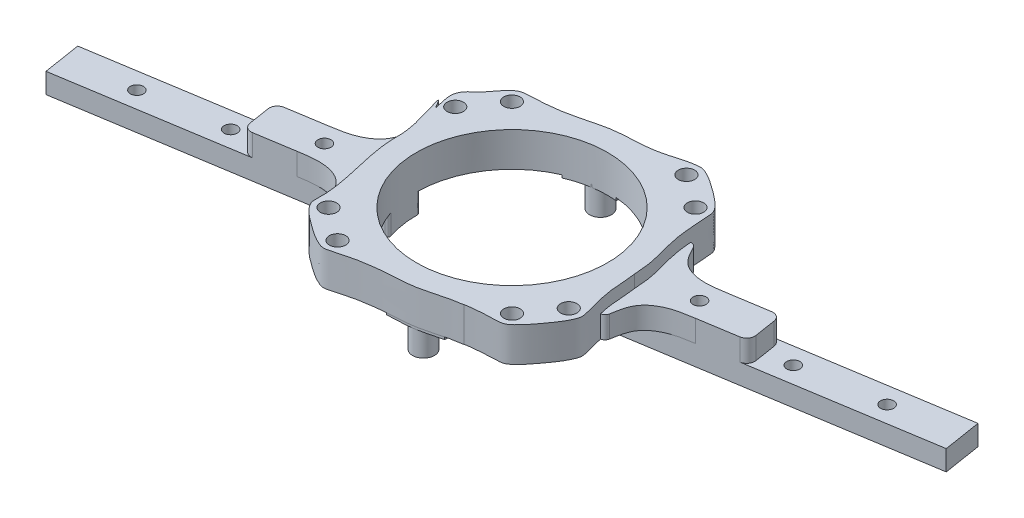
SolidWorks part; units mm, degrees
ref_plane "前视基准面" through (0, 0, 0) normal (0, 0, 1) x (1, 0, 0)
ref_plane "上视基准面" through (0, 0, 0) normal (0, 1, 0) x (1, 0, 0)
ref_plane "右视基准面" through (0, 0, 0) normal (1, 0, 0) x (0, 0, -1)
sketch "草图1" plane through (0, 0, 0) normal (0, 1, 0) x (1, 0, 0)
  circle A0 centre (0, 0) radius 17.5
  circle A1 centre (0, 0) radius 18.901
  dimension "D1" = 35
extrude "凸台-拉伸1" add sketch "草图1" along normal blind 2
sketch "草图2" plane through (0, 0, 0) normal (0, -1, 0) x (1, 0, 0)
  circle A0 centre (-10.7739, 21.1656) radius 1.5
  circle A1 centre (16.8004, 16.7872) radius 1.5
  circle A2 centre (21.1656, 10.7739) radius 1.5
  circle A3 centre (16.7872, -16.8004) radius 1.5
  circle A4 centre (10.7739, -21.1656) radius 1.5
  circle A5 centre (-16.8004, -16.7872) radius 1.5
  circle A6 centre (-21.1656, -10.7739) radius 1.5
  circle A7 centre (-16.7872, 16.8004) radius 1.5
  circle A28 centre (0, 0) radius 17.5
  spline S3 degree 3 poles (11.007, 19.7796) (11.3114, 19.6784) (14.2307, 19.3249) (16.1426, 19.3879) (17.8124, 19.1708) (19.4344, 17.903) (21.2548, 15.4236) (23.0457, 12.9332) (23.7495, 10.9887) (23.274, 8.5261) (21.9734, 4.7628) (22.0269, 1.1873) (21.7447, -0.683) knots 0 0 0 0 0.101498 0.202996 0.236379 0.269761 0.41266 0.555558 0.58894 0.622323 0.811161 1 1 1 1
  spline S4 degree 3 poles (21.7447, -0.683) (21.6101, -1.5752) (21.6055, -3.3542) (20.6884, -6.8809) (19.4904, -11.3054) (19.4855, -15.3122) (19.178, -17.8032) (17.9056, -19.4334) (15.4365, -21.2528) (12.9718, -22.9922) (11.1783, -23.6905) (8.6855, -23.5473) (4.924, -21.9674) (0.2192, -21.8124) (-3.3386, -21.5662) (-6.4463, -20.811) (-9.0785, -20.0903) (-12.7412, -19.4848) (-15.1253, -19.3752) (-17.5836, -19.2474) (-19.4002, -18.127) (-20.9244, -15.1209) (-24.3676, -13.3124) (-22.2966, -7.7817) (-24.7387, -12.2711) (-21.435, -3.3276) (-22.0126, 0.3206) (-20.5515, 8.1406) (-19.1109, 13.0019) (-19.2816, 16.8284) knots 0 0 0 0 0.02817 0.053916 0.112305 0.168269 0.178162 0.188055 0.230405 0.272754 0.280796 0.288838 0.34856 0.404524 0.432694 0.45844 0.502911 0.516855 0.572819 0.576577 0.592462 0.634812 0.677161 0.707499 0.719914 0.775878 0.831843 0.888071 1 1 1 1
  spline S5 degree 3 poles (-19.2816, 16.8284) (-19.323, 17.5174) (-18.1907, 19.2578) (-15.4061, 21.2421) (-12.9273, 23.0421) (-10.9838, 23.7431) (-9.3566, 23.4387) (-7.2233, 22.7077) (-4.4614, 22.2162) (-1.8337, 21.8607) (0.7732, 21.7432) (3.3794, 21.5754) (7.3403, 20.5662) (8.6858, 20.19) (9.8558, 19.9936) (10.7406, 19.8682) (11.007, 19.7796) knots 0 0 0 0 0.047987 0.150696 0.253406 0.277399 0.301393 0.374345 0.447298 0.510152 0.573007 0.641327 0.709648 0.853023 0.882058 1 1 1 1
  dimension "D1" = 3
extrude "凸台-拉伸2" add sketch "草图2" along normal blind 4.3 and the other way blind 2
sketch "草图3" plane through (0, -4.3, 0) normal (0, -1, 0) x (1, 0, 0)
  line L0 (4.6838, 9.8878) -> (-47.2443, 18.1334) construction
  line L1 (3.0581, 19.2587) -> (0, 0) construction
  line L2 (0, 0) -> (-3.0579, -19.2577) construction
  line L3 (-4.7873, -9.8704) -> (47.1409, -18.1159) construction
  circle A0 centre (3.0581, 19.2587) radius 2
  circle A1 centre (3.0581, 19.2587) radius 9 construction
  circle A2 centre (-3.0579, -19.2577) radius 2
  circle A3 centre (-3.0579, -19.2577) radius 9 construction
  dimension "D1" = 18
  dimension "D2" = 4
  dimension "D3" = 18
  dimension "D4" = 4
extrude "凸台-拉伸3" add sketch "草图3" along normal blind 5
sketch "草图5" plane through (0, -4.3, 0) normal (0, -1, 0) x (1, 0, 0)
  line L0 (0, 0) -> (38.9853, -6.1904) construction
  line L1 (70.6703, -14.0546) -> (-71.5479, 8.5279) construction
  circle A0 centre (3.0581, 19.2587) radius 5 construction
  arc A1 (-1.5944, 17.4272) -> (6.9144, 16.0761) centre (0, 0) cw
  arc A2 (-2.6852, -17.2928) -> (2.7444, 17.2835) centre (0, 0) ccw construction
  arc A3 (-1.3158, 21.6815) -> (-1.5944, 17.4272) centre (3.0581, 19.2587) ccw
  arc A4 (7.9454, 20.3141) -> (6.9144, 16.0761) centre (3.0581, 19.2587) cw
  arc A5 (-7.9672, -20.2075) -> (-6.9144, -16.0761) centre (-3.0581, -19.2587) cw
  arc A6 (-6.9144, -16.0761) -> (1.5944, -17.4272) centre (0, 0) ccw
  arc A7 (1.262, -21.7761) -> (1.5944, -17.4272) centre (-3.0581, -19.2587) ccw
  spline S0 degree 3 poles (-1.3158, 21.6815) (-0.2135, 21.5939) (1.3807, 21.5885) (3.4585, 21.3907) (5.444, 20.9684) (6.9168, 20.5202) (7.9454, 20.3141) knots 0 0 0 0 0.352817 0.508743 0.665414 1 1 1 1
  spline S2 degree 3 poles (-7.9672, -20.2075) (-6.892, -20.4656) (-5.3746, -20.9543) (-3.3377, -21.4099) (-1.319, -21.6234) (0.2201, -21.6535) (1.262, -21.7761) knots 0 0 0 0 0.352817 0.508743 0.665414 1 1 1 1
  dimension "D1" = 10
extrude "凸台-拉伸5" add sketch "草图5" along normal blind 0.5
sketch "草图6" plane through (0, -4.3, 0) normal (0, -1, 0) x (1, 0, 0)
  line L0 (0, 0) -> (83.2876, -13.2251) construction
  line L1 (70.6703, -14.0546) -> (-71.5479, 8.5279) construction
  line L2 (0, 0) -> (7.0837, 44.6111) construction
  line L3 (22.6545, 6.4264) -> (16.7134, 7.3698)
  line L4 (32.0065, -1.5404) -> (39.048, -2.6585)
  line L5 (71.6577, -7.8366) -> (-70.5606, 14.746) construction
  line L6 (-30.9094, 8.4499) -> (-37.9509, 9.5679)
  line L7 (40.2942, -4.3752) -> (39.9809, -6.3485)
  line L8 (19.5496, -13.1279) -> (13.6084, -12.1845)
  line L9 (30.9094, -8.4499) -> (37.9509, -9.5679)
  line L10 (39.6675, -8.3217) -> (39.9809, -6.3485)
  line L11 (-39.6675, 8.3217) -> (-39.9809, 6.3485)
  line L12 (-40.2942, 4.3752) -> (-39.9809, 6.3485)
  line L13 (-32.0065, 1.5404) -> (-39.048, 2.6585)
  line L14 (-19.5496, 13.1279) -> (-13.6084, 12.1845)
  line L15 (-22.6545, -6.4264) -> (-16.7134, -7.3698)
  circle A0 centre (21.1656, 10.7739) radius 2.5 construction
  arc A1 (1.5944, -17.4272) -> (6.9144, 16.0761) centre (0, 0) ccw construction
  arc A2 (13.3066, -11.3659) -> (16.1729, 6.685) centre (0, 0) ccw
  arc A3 (23.4842, 5.6027) -> (22.6545, 6.4264) centre (22.4977, 5.4388) ccw
  arc A4 (16.7134, 7.3698) -> (16.1729, 6.685) centre (16.6349, 6.876) ccw
  arc A5 (39.048, -2.6585) -> (40.2942, -4.3752) centre (38.8128, -4.14) cw
  arc A6 (13.6084, -12.1845) -> (13.3066, -11.3659) centre (13.6868, -11.6907) cw
  arc A7 (20.5935, -12.6017) -> (19.5496, -13.1279) centre (19.7064, -12.1402) cw
  arc A8 (37.9509, -9.5679) -> (39.6675, -8.3217) centre (38.1861, -8.0865) ccw
  arc A9 (-37.9509, 9.5679) -> (-39.6675, 8.3217) centre (-38.1861, 8.0865) ccw
  arc A10 (-39.048, 2.6585) -> (-40.2942, 4.3752) centre (-38.8128, 4.14) cw
  arc A11 (-20.5935, 12.6017) -> (-19.5496, 13.1279) centre (-19.7064, 12.1402) cw
  arc A12 (-13.6084, 12.1845) -> (-13.3066, 11.3659) centre (-13.6868, 11.6907) cw
  arc A13 (-16.1729, -6.685) -> (-13.3066, 11.3659) centre (0, 0) cw
  arc A14 (-16.7134, -7.3698) -> (-16.1729, -6.685) centre (-16.6349, -6.876) ccw
  arc A15 (-23.4842, -5.6027) -> (-22.6545, -6.4264) centre (-22.6575, -5.5997) ccw
  spline S0 degree 3 poles (20.5935, -12.6017) (20.8165, -12.1731) (21.4171, -11.0059) (22.8603, -8.9685) (26.5188, -7.7575) (29.1956, -8.1777) (30.9094, -8.4499) knots 0.057026 0.057026 0.057026 0.057026 0.169435 0.36028 0.616457 1 1 1 1
  spline S1 degree 3 poles (23.4842, 5.6027) (23.5634, 5.1261) (23.7729, 3.8302) (24.514, 1.446) (27.6174, -0.8387) (30.2927, -1.2683) (32.0065, -1.5404) knots 0.057026 0.057026 0.057026 0.057026 0.169435 0.36028 0.616457 1 1 1 1
  spline S2 degree 3 poles (-23.4842, -5.6027) (-23.5634, -5.1261) (-23.7729, -3.8302) (-24.514, -1.446) (-27.6174, 0.8387) (-30.2927, 1.2683) (-32.0065, 1.5404) knots 0.057026 0.057026 0.057026 0.057026 0.169435 0.36028 0.616457 1 1 1 1
  spline S3 degree 3 poles (-20.5935, 12.6017) (-20.8165, 12.1731) (-21.4171, 11.0059) (-22.8603, 8.9685) (-26.5188, 7.7575) (-29.1956, 8.1777) (-30.9094, 8.4499) knots 0.057026 0.057026 0.057026 0.057026 0.169435 0.36028 0.616457 1 1 1 1
  point P34 (15.8047, 7.514)
  dimension "D1" = 5
  dimension "D2" = 1
  dimension "D3" = 0.5
  dimension "D4" = 1.5
extrude "凸台-拉伸6" add sketch "草图6" against normal blind 4 separate body
sketch "草图7" plane through (0, -4.3, 0) normal (0, -1, 0) x (1, 0, 0)
  line L0 (17.2287, -6.2775) -> (70.5606, -14.746)
  line L1 (17.2287, -6.2775) -> (18.3258, 0.6319) construction
  line L2 (70.5606, -14.746) -> (71.6577, -7.8366)
  line L3 (18.3258, 0.6319) -> (71.6577, -7.8366)
  line L4 (17.2287, -6.2775) -> (71.6577, -7.8366) construction
  line L5 (70.5606, -14.746) -> (18.3258, 0.6319) construction
  line L6 (71.6577, -7.8366) -> (-70.5606, 14.746) construction
  line L7 (71.6266, -8.0321) -> (70.5916, -14.5504) construction
  line L8 (18.3258, 0.6319) -> (18.0775, 0.6713)
  line L9 (17.2287, -6.2775) -> (16.9804, -6.2381)
  line L10 (70.5606, -14.746) -> (-71.6577, 7.8366) construction
  line L11 (0, 0) -> (5.947, 37.4527) construction
  line L12 (-71.6577, 7.8366) -> (-70.5606, 14.746)
  line L13 (-17.2287, 6.2775) -> (-70.5606, 14.746)
  line L14 (-18.3258, -0.6319) -> (-71.6577, 7.8366)
  line L15 (-18.3258, -0.6319) -> (-18.0775, -0.6713)
  line L16 (-17.2287, 6.2775) -> (-16.9804, 6.2381)
  arc A0 (1.5944, -17.4272) -> (6.9144, 16.0761) centre (0, 0) ccw construction
  arc A1 (17.4991, 0.1726) -> (16.585, -5.5847) centre (0, 0) cw
  arc A2 (16.9804, -6.2381) -> (16.585, -5.5847) centre (17.0588, -5.7443) cw
  arc A3 (18.0775, 0.6713) -> (17.4991, 0.1726) centre (17.9991, 0.1775) ccw
  arc A4 (-18.0775, -0.6713) -> (-17.4991, -0.1726) centre (-17.9991, -0.1775) ccw
  arc A5 (-16.9804, 6.2381) -> (-16.585, 5.5847) centre (-17.0588, 5.7443) cw
  arc A6 (-16.585, 5.5847) -> (-17.4991, -0.1726) centre (0, 0) ccw
  point P1 (44.4432, -7.057)
  point P20 (16.3861, -6.1437)
  point P23 (17.4832, 0.7657)
  dimension "D1" = 0.5
extrude "凸台-拉伸7" add sketch "草图7" along normal up to surface (3.7 mm away)
sketch "草图8" plane through (0, -8, 0) normal (0, -1, 0) x (1, 0, 0)
  circle A0 centre (59.2576, -9.4094) radius 1.2
  circle A1 centre (44.4432, -7.057) radius 1.2
  circle A2 centre (29.6288, -4.7047) radius 1.2
  circle A3 centre (-29.6288, 4.7047) radius 1.2
  circle A4 centre (-44.4432, 7.057) radius 1.2
  circle A5 centre (-59.2576, 9.4094) radius 1.2
  dimension "D1" = 2.4
extrude "切除-拉伸1" cut sketch "草图8" against normal through all
